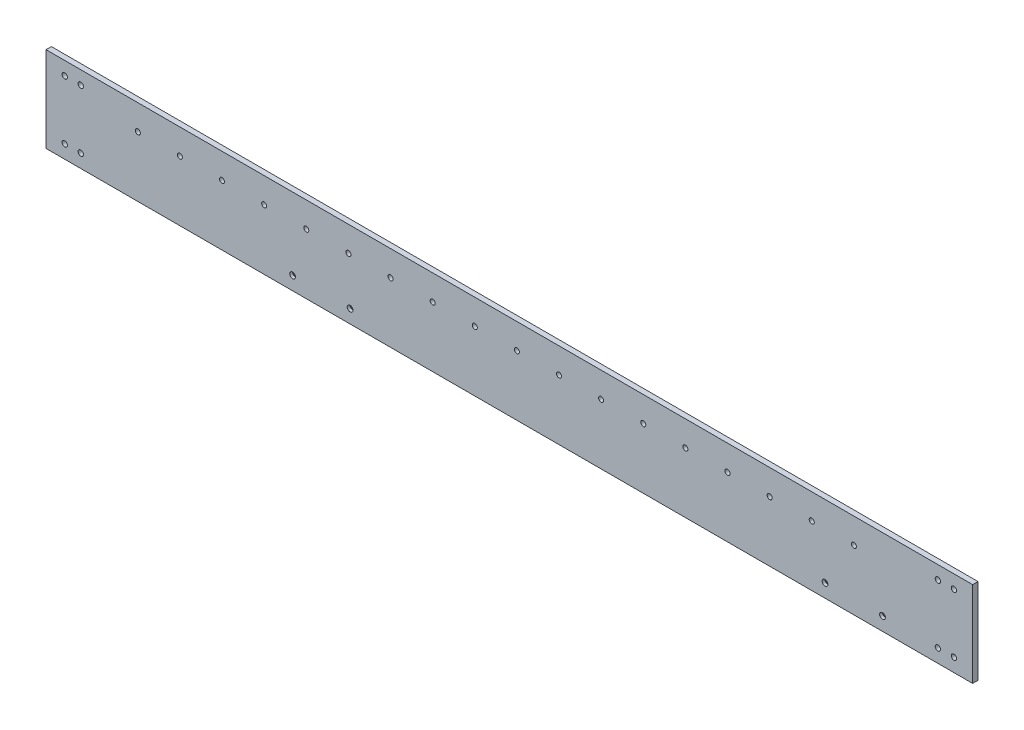
SolidWorks part; units mm, degrees
ref_plane "Front Plane" through (0, 0, 0) normal (0, 0, 1) x (1, 0, 0)
ref_plane "Top Plane" through (0, 0, 0) normal (0, 1, 0) x (1, 0, 0)
ref_plane "Right Plane" through (0, 0, 0) normal (1, 0, 0) x (0, 0, -1)
sketch "Sketch1" plane through (0, 0, 0) normal (1, 0, 0) x (0, 0, -1)
  line L0 (0, 0) -> (-3.175, 0)
  line L3 (-3.175, 0) -> (-3.175, 50.8)
  line L4 (-3.175, 50.8) -> (0, 50.8)
  line L5 (0, 50.8) -> (0, 0)
  dimension "LHeight" = 50.8
  dimension "LMaterialThickness" = 3.175
extrude "Boss-Extrude1" add sketch "Sketch1" along normal blind 550
sketch "SideHoles-Sketch4" plane through (0, 0, 3.175) normal (0, 0, 1) x (1, 0, 0)
  line L0 (550, 50.8) -> (0, 50.8) construction
  line L1 (550, 50.8) -> (550, 0) construction
  line L2 (0, 50.8) -> (0, 0) construction
  line L3 (550, 50.8) -> (0, 50.8) construction
  line L4 (550, 0) -> (0, 0) construction
  line L6 (0, 50.8) -> (0, 0) construction
  line L7 (550, 50.8) -> (550, 0) construction
  circle A1 centre (11.1125, 42.8625) radius 1.5875
  circle A3 centre (529.3625, 42.8625) radius 1.5875
  circle A4 centre (20.6375, 42.8625) radius 1.5875
  circle A5 centre (538.8875, 42.8625) radius 1.5875
  circle A6 centre (11.1125, 7.9375) radius 1.5875
  circle A7 centre (20.6375, 7.9375) radius 1.5875
  circle A8 centre (529.3625, 7.9375) radius 1.5875
  circle A9 centre (538.8875, 7.9375) radius 1.5875
  circle A10 centre (54.5, 35.8) radius 1.5
  circle A11 centre (79.5, 35.8) radius 1.5
  circle A12 centre (104.5, 35.8) radius 1.5
  circle A13 centre (129.5, 35.8) radius 1.5
  circle A14 centre (154.5, 35.8) radius 1.5
  circle A15 centre (179.5, 35.8) radius 1.5
  circle A16 centre (204.5, 35.8) radius 1.5
  circle A17 centre (229.5, 35.8) radius 1.5
  circle A18 centre (254.5, 35.8) radius 1.5
  circle A19 centre (279.5, 35.8) radius 1.5
  circle A20 centre (304.5, 35.8) radius 1.5
  circle A21 centre (329.5, 35.8) radius 1.5
  circle A22 centre (354.5, 35.8) radius 1.5
  circle A23 centre (379.5, 35.8) radius 1.5
  circle A24 centre (496.4875, 7.9375) radius 1.5875
  circle A26 centre (180.4875, 7.9375) radius 1.5875
  circle A29 centre (404.5, 35.8) radius 1.5
  circle A30 centre (429.5, 35.8) radius 1.5
  circle A31 centre (454.5, 35.8) radius 1.5
  circle A32 centre (479.5, 35.8) radius 1.5
  circle A34 centre (146.3625, 7.9375) radius 1.5875
  circle A36 centre (462.3625, 7.9375) radius 1.5875
  dimension "D2" = 3.175
  dimension "D10" = 3
  dimension "D14" = 3.175
  dimension "D4" = 7.9375
  dimension "D3" = 11.1125
  dimension "D5" = 20.6375
  dimension "D1" = 11.1125
  dimension "D6" = 20.6375
  dimension "D7" = 7.9375
  dimension "D8" = 54.5
  dimension "D12" = 25
  dimension "D15" = 7.9375
  dimension "D17" = 53.5125
  dimension "D18" = 316
  dimension "D13" = 34.125
  dimension "D16" = 34.125
  dimension "D9" = 15
  dimension "D11" = 18
extrude "SideHoles-Cut-Extrude3" cut sketch "SideHoles-Sketch4" against normal through all
sketch "Sketch2" plane through (0, 0, 0) normal (0, 0, -1) x (-1, 0, 0)
  point P0 (-496.4875, 7.9375)
  point P3 (-462.3625, 7.9375)
  point P6 (-180.4875, 7.9375)
  point P9 (-146.3625, 7.9375)
hole_wizard "CSK for M3 Flat Head Machine Screw1" positions "Sketch2" profile "Sketch3" countersink size "M3" standard "ANSI Metric" end condition through all
sketch "Sketch3" plane through (496.4875, 7.9375, 0) normal (1, 0, 0) x (0, 1, 0)
  line L0 (0, 0) -> (0, 3.175)
  line L1 (0, 3.175) -> (1.7, 3.175)
  line L2 (1.7, 3.175) -> (1.7, 1.45)
  line L3 (1.7, 1.45) -> (3.15, 0)
  line L5 (3.15, 0) -> (0, 0)
  line L6 (-1.7, 1.45) -> (-3.15, 0) construction
  line L11 (0, -6.35) -> (0, 107.95) construction
  dimension "Thru Hole Dia." = 3.4
  dimension "Thru Hole Depth" = 3.175
  dimension "Near C'Sink Dia." = 6.3
  dimension "Near C'Sink Angle" = 90
equation "\"MidLeftOrRightSideRailHeight\"= 2.0in"
equation "\"RailThickness\"= .125in'Spec"
equation "\"SideRailHoleY1FromEdge\"= \"HoleOffsetFromEdge\""
equation "\"SideRailHoleX1FromSide\"= \"HoleOffsetFromSide\""
equation "\"MidSideRailLength\"= \"SideRailLength\""
equation "\"VSWidth\"= 1.25in'Spec"
equation "\"HoleOffsetFromEdge\"= \"RailThickness\" * 2.5"
equation "\"HoleOffsetFromSide\"= \"RailThickness\" * 3.5"
equation "\"SideRailHoleX2FromSide\"= \"VSWidth\" - \"HoleOffsetFromEdge\" - \"RailThickness\"'Equals 20.6375"
equation "\"FasteningHoleDiameter\"= .125in"
equation "\"StepperWidth\"= 42mm'Spec"
equation "\"D2@SideHoles-Sketch4\"=\"FasteningHoleDiameter\""
equation "\"LHeight@Sketch1\"=\"MidLeftOrRightSideRailHeight\""
equation "\"LMaterialThickness@Sketch1\"=\"RailThickness\""
equation "\"D1@Boss-Extrude1\"=\"MidSideRailLength\""
equation "\"D4@SideHoles-Sketch4\"=\"SideRailHoleY1FromEdge\""
equation "\"D3@SideHoles-Sketch4\"=\"SideRailHoleX1FromSide\" "
equation "\"D5@SideHoles-Sketch4\"=\"SideRailHoleX2FromSide\" "
equation "\"D1@SideHoles-Sketch4\"=\"SideRailHoleX1FromSide\" "
equation "\"D6@SideHoles-Sketch4\"=\"SideRailHoleX2FromSide\""
equation "\"LinearRailXMountHole\"= \"StepperWidth\" + \"LinearRailFirstHoleOffsetFromEdge\""
equation "\"D8@SideHoles-Sketch4\"=\"LinearRailXMountHole\""
equation "\"LinearRailHoleDistance\"= 25mm'Spec"
equation "\"D12@SideHoles-Sketch4\"=\"LinearRailHoleDistance\""
equation "\"SideRailLength\"= 550mm"
equation "\"LinearRailFirstHoleOffsetFromEdge\"= 12.5mm'Spec"
equation "\"D7@SideHoles-Sketch4\"= \"MidRailRodStabilizerMountingHoleOffsetFromEdge\""
equation "\"DistanceFromBedFrontToFirstLeftStepperHole\"= \"LeadScrewNutPadSize\" + 10mm'Equals 34"
equation "\"BeltTensionerDepth\"= \"BeltTensionerBackWallThickness\" + \"BeltTensionerInnerDepth\"'Equals 23.4"
equation "\"20TGT2PulleyDiameter\"= 17.9mm'Spec"
equation "\"BeltTensionerSpaceBetweenPulleyAndWall\"= 1.5mm"
equation "\"BeltTensionerBackWallThickness\"= 4mm"
equation "\"BeltTensionerInnerDepth\"= \"20TGT2PulleyDiameter\" + \"BeltTensionerSpaceBetweenPulleyAndWall\""
equation "\"DistanceFromFrontSideToBedFront\"= \"RailThickness\" + \"BeltTensionerDepth\" + 10mm'Equals 36.575"
equation "\"DistanceBetweenFrontToBackStepperHoles\"= \"BedLength\" - \"DistanceFromBedFrontToFirstLeftStepperHole\"'Equals 316"
equation "\"BedLength\"= \"BedInnerSquareLength\" + \"BedLWidth\" * 2 + \"BedIncreasedByLength\"'Equals 350"
equation "\"BedThirdSize\"= 70mm"
equation "\"BedInnerSquareWidth\"= \"BedThirdSize\" * 3'Equals 210"
equation "\"BedLWidth\"= \"BedThirdSize\"'Equals 70"
equation "\"BedIncreasedByLength\"= 0mm"
equation "\"D14@SideHoles-Sketch4\"= \"FasteningHoleDiameter\""
equation "\"D15@SideHoles-Sketch4\"= \"HoleOffsetFromEdge\""
equation "\"BedInnerSquareLength\"= \"BedInnerSquareWidth\""
equation "\"DistanceFromFrontSideToFirstLeftStabilizerMountingHole\"= \"DistanceFromFrontSideToFirstLeftStepperHole\" - \"DistanceFromStepperHoleToRodStabilizerMountingHole\"'Equals 53.5125"
equation "\"DistanceFromFrontSideToFirstLeftStepperHole\"= \"DistanceFromFrontSideToBedFront\" + \"DistanceFromBedFrontToFirstLeftStepperHole\"'Equals 70.575"
equation "\"LeadScrewNutMountingHoleFlangeDiameter\"= 22mm'Spec"
equation "\"LeadScrewNutPadSize\"= \"LeadScrewNutMountingHoleFlangeDiameter\" + 2mm'Equals 24"
equation "\"D17@SideHoles-Sketch4\"=\"DistanceFromFrontSideToFirstLeftStabilizerMountingHole\""
equation "\"D18@SideHoles-Sketch4\"=\"DistanceBetweenFrontToBackStepperHoles\""
equation "\"MidRailRodStabilizerMountingHoleOffsetFromEdge\"= \"HoleOffsetFromEdge\""
equation "\"RodStabilizerLength\"= 50mm"
equation "\"DistanceFromStepperHoleToRodStabilizerMountingHole\"= \"RodStabilizerLength\" / 2 - \"HoleOffsetFromEdge\"'Equals 17.0625"
equation "\"D13@SideHoles-Sketch4\"=\"RodStabilizerLength\" - \"HoleOffsetFromEdge\" * 2"
equation "\"D16@SideHoles-Sketch4\"=\"RodStabilizerLength\" - \"HoleOffsetFromEdge\" *2"
equation "\"LinearRailWidth\"= 12mm'Spec"
equation "\"MidSideRailVerticalOffset\"= \"LinearRailWidth\" + 3mm'Allows space for RodStabilizer to attach to bottom of MidSideRail"
equation "\"D9@SideHoles-Sketch4\"=\"MidSideRailVerticalOffset\""
